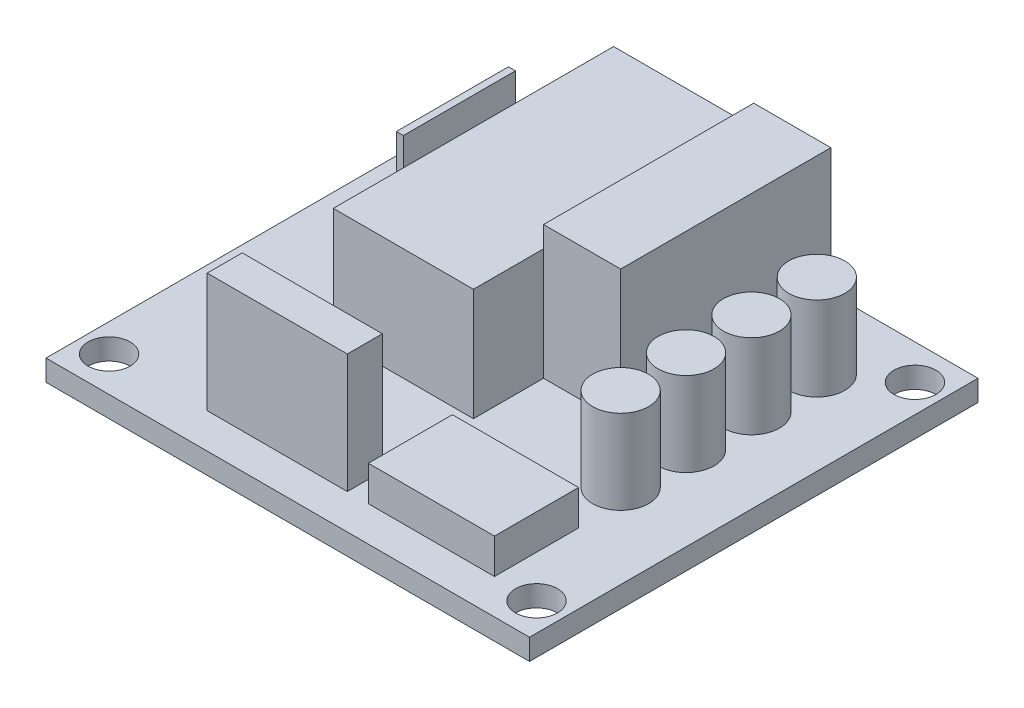
SolidWorks part; units mm, degrees
ref_plane "Front" through (0, 0, 0) normal (0, 0, 1) x (1, 0, 0)
ref_plane "Top" through (0, 0, 0) normal (0, 1, 0) x (1, 0, 0)
ref_plane "Right" through (0, 0, 0) normal (1, 0, 0) x (0, 0, -1)
sketch "Эскиз1" plane through (0, 0, 0) normal (0, 1, 0) x (1, 0, 0)
  line L0 (0, 16) -> (0, -16) construction
  line L1 (-17.25, 16) -> (17.25, 16)
  line L2 (-17.25, 16) -> (-17.25, -16)
  line L3 (-17.25, -16) -> (17.25, -16)
  line L4 (17.25, 16) -> (17.25, -16)
  line L5 (-17.25, 16) -> (17.25, -16) construction
  line L6 (-17.25, -16) -> (17.25, 16) construction
  line L7 (-17.25, 0) -> (17.25, 0) construction
  line L8 (11.25, 16) -> (11.25, -16) construction
  line L9 (11.25, -1.5) -> (11.25, -0.8333) construction
  line L10 (11.25, 3.1667) -> (11.25, 3.8333) construction
  line L11 (11.25, 7.8333) -> (11.25, 8.5) construction
  line L13 (-8.25, 15.5) -> (1.75, 15.5)
  line L14 (-8.25, 15.5) -> (-8.25, -4.5)
  line L15 (-8.25, -4.5) -> (1.75, -4.5)
  line L16 (1.75, 15.5) -> (1.75, -4.5)
  line L17 (-8.25, 15.5) -> (1.75, -4.5) construction
  line L18 (-8.25, -4.5) -> (1.75, 15.5) construction
  line L19 (1.75, 15.5) -> (7.25, 15.5)
  line L20 (1.75, 15.5) -> (1.75, 0.5)
  line L21 (1.75, 0.5) -> (7.25, 0.5)
  line L22 (7.25, 15.5) -> (7.25, 0.5)
  line L23 (1.75, 15.5) -> (7.25, 0.5) construction
  line L24 (1.75, 0.5) -> (7.25, 15.5) construction
  line L25 (-9.25, 11.5) -> (-11.75, 11.5)
  line L26 (-9.25, 11.5) -> (-9.25, 1.5)
  line L27 (-9.25, 1.5) -> (-11.75, 1.5)
  line L28 (-11.75, 11.5) -> (-11.75, 1.5)
  line L29 (-8.25, -11) -> (1.75, -11)
  line L30 (-8.25, -11) -> (-8.25, -13.5)
  line L31 (-8.25, -13.5) -> (1.75, -13.5)
  line L32 (1.75, -11) -> (1.75, -13.5)
  line L33 (3.25, -7.5) -> (12.25, -7.5)
  line L34 (3.25, -7.5) -> (3.25, -13.5)
  line L35 (3.25, -13.5) -> (12.25, -13.5)
  line L36 (12.25, -7.5) -> (12.25, -13.5)
  line L37 (-9.25, 11.5) -> (-11.75, 1.5) construction
  line L38 (-9.25, 1.5) -> (-11.75, 11.5) construction
  line L39 (-10.25, 10.5) -> (-10.75, 10.5)
  line L40 (-10.25, 10.5) -> (-10.25, 2.5)
  line L41 (-10.25, 2.5) -> (-10.75, 2.5)
  line L42 (-10.75, 10.5) -> (-10.75, 2.5)
  line L43 (-10.25, 10.5) -> (-10.75, 2.5) construction
  line L44 (-10.25, 2.5) -> (-10.75, 10.5) construction
  circle A0 centre (-15.25, 13.5) radius 1.5
  circle A1 centre (15.25, 13.5) radius 1.5
  circle A2 centre (15.25, -13.5) radius 1.5
  circle A3 centre (-15.25, -13.5) radius 1.5
  circle A4 centre (11.25, 10.5) radius 2
  circle A5 centre (11.25, 5.8333) radius 2
  circle A6 centre (11.25, 1.1667) radius 2
  circle A7 centre (11.25, -3.5) radius 2
  point P0 (0, 0)
  point P34 (-3.25, 5.5)
  point P39 (4.5, 8)
  point P44 (-10.5, 6.5)
  point P57 (-10.5, 6.5)
  dimension "D3" = 3
  dimension "D6" = 4
  dimension "D10" = 0.5
  dimension "D1" = 34.5
  dimension "D2" = 32
  dimension "D4" = 2.5
  dimension "D5" = 2
  dimension "D7" = 6
  dimension "D8" = 5.5
  dimension "D9" = 12.5
  dimension "D11" = 0.5
  dimension "D12" = 15
  dimension "D13" = 5.5
  dimension "D14" = 10
  dimension "D15" = 10
  dimension "D16" = 20
  dimension "D17" = 0.5
  dimension "D18" = 8
  dimension "D19" = 10
  dimension "D20" = 2.5
  dimension "D21" = 5.5
  dimension "D22" = 4.5
  dimension "D23" = 10
  dimension "D24" = 2.5
  dimension "D25" = 6
  dimension "D26" = 9
  dimension "D27" = 5
  dimension "D28" = 2.5
  dimension "D29" = 9
  dimension "D30" = 2.5
extrude "Бобышка-Вытянуть1" add sketch "Эскиз1" against normal blind 1.5 contours L4 L1 L2 L3 A7 A6 A5 A4 A3 A2 A1 A0 L28 L25 L26 L27 L19 L22 L21 L16 L15 L14 L13 L29 L32 L31 L30 L33 L36 L35 L34 | L25 L28 L27 L26 L42 L39 L40 L41 | L39 L42 L41 L40 | L16 L13 L14 L15 | L22 L19 L16 L21 | A4 | A5 | A6 | A7 | L36 L33 L34 L35 | L32 L29 L30 L31 region at (0, 0, -15.5294) region at (-3.25, 0, -5.5) region at (4.5, 0, -8) region at (-9.3531, 0, -6.5) region at (-3.25, 0, 12.25) region at (7.75, 0, 10.5) region at (-10.5, 0, -6.5) region at (11.25, 0, -10.5) region at (11.25, 0, -5.8333) region at (11.25, 0, -1.1667) region at (11.25, 0, 3.5)
extrude "Бобышка-Вытянуть2" add sketch "Эскиз1<3>" along normal blind 6 contours A5 | A4 | A6 | A7 region at (11.25, 0, -10.5) region at (11.25, 0, -5.8333) region at (11.25, 0, -1.1667) region at (11.25, 0, 3.5)
sketch "Эскиз1<3>" plane through (0, 0, 0) normal (0, 1, 0) x (1, 0, 0) same geometry as "Эскиз1"
extrude "Бобышка-Вытянуть3" add sketch "Эскиз1<4>" along normal blind 2.5 contours L36 L33 L34 L35 region at (7.75, 0, 10.5)
sketch "Эскиз1<4>" plane through (0, 0, 0) normal (0, 1, 0) x (1, 0, 0) same geometry as "Эскиз1"
extrude "Бобышка-Вытянуть4" add sketch "Эскиз1<5>" along normal blind 8.5 contours L32 L29 L30 L31 region at (-3.25, 0, 12.25)
sketch "Эскиз1<5>" plane through (0, 0, 0) normal (0, 1, 0) x (1, 0, 0) same geometry as "Эскиз1"
extrude "Бобышка-Вытянуть5" add sketch "Эскиз1<6>" along normal blind 9.5 contours L22 L19 L16 L21 region at (4.5, 0, -8)
sketch "Эскиз1<6>" plane through (0, 0, 0) normal (0, 1, 0) x (1, 0, 0) same geometry as "Эскиз1"
extrude "Бобышка-Вытянуть6" add sketch "Эскиз1<7>" along normal blind 8 contours L16 L13 L14 L15 region at (-3.25, 0, -5.5)
sketch "Эскиз1<7>" plane through (0, 0, 0) normal (0, 1, 0) x (1, 0, 0) same geometry as "Эскиз1"
extrude "Бобышка-Вытянуть7" add sketch "Эскиз1<9>" along normal blind 8 contours L39 L42 L41 L40 region at (-10.5, 0, -6.5)
sketch "Эскиз1<9>" plane through (0, 0, 0) normal (0, 1, 0) x (1, 0, 0) same geometry as "Эскиз1"
extrude "Бобышка-Вытянуть8" add sketch "Эскиз1<10>" along normal blind 2.5 contours L25 L28 L27 L26 L42 L39 L40 L41 region at (-9.3531, 0, -6.5)
sketch "Эскиз1<10>" plane through (0, 0, 0) normal (0, 1, 0) x (1, 0, 0) same geometry as "Эскиз1"
